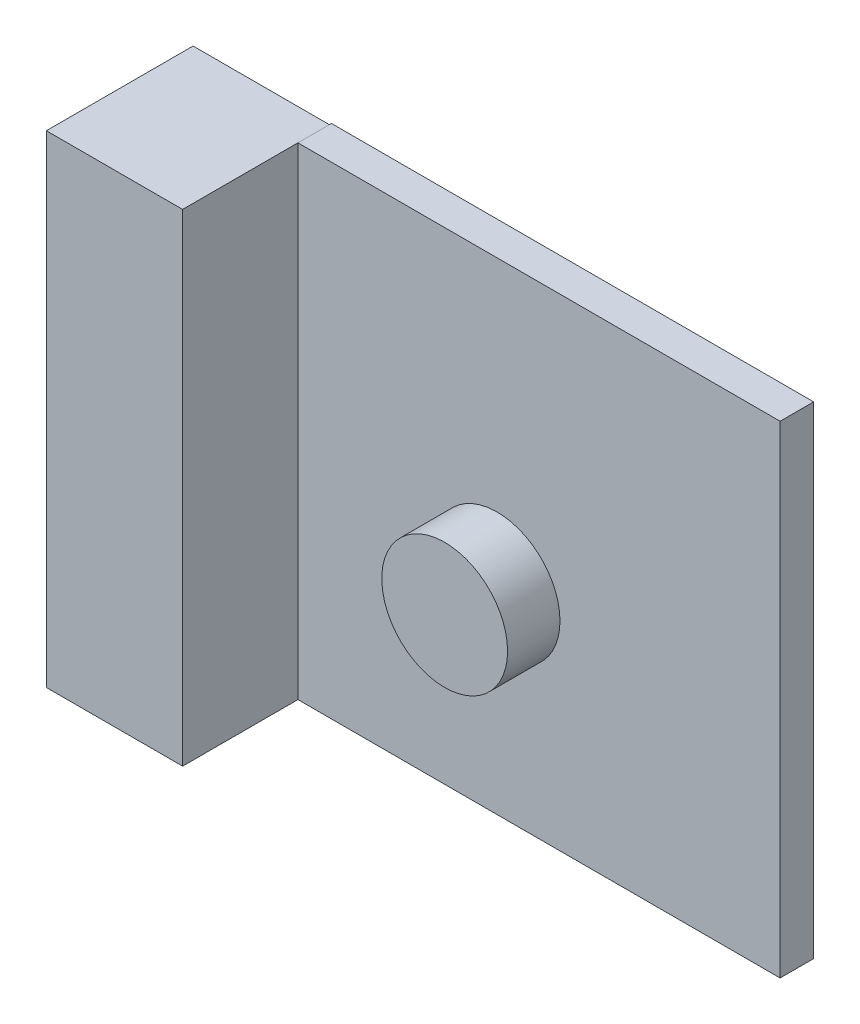
SolidWorks part; units mm, degrees
ref_plane "Front Plane" through (0, 0, 0) normal (0, 0, 1) x (1, 0, 0)
ref_plane "Top Plane" through (0, 0, 0) normal (0, 1, 0) x (1, 0, 0)
ref_plane "Right Plane" through (0, 0, 0) normal (1, 0, 0) x (0, 0, -1)
other "Configuration Table"
sketch "Sketch1" plane through (0, 0, 0) normal (0, 0, 1) x (1, 0, 0)
  circle A0 centre (58, 130) radius 3
extrude "magnet" add sketch "Sketch1" along normal blind 2.5 from offset 35.5 separate body offset against normal yes
sketch "Sketch2" plane through (0, 0, 0) normal (1, 0, 0) x (0, 0, -1)
  line L1 (39.1, 118.5) -> (37.5, 118.5)
  line L2 (39.1, 118.5) -> (39.1, 141.5)
  line L3 (39.1, 141.5) -> (37.5, 141.5)
  line L4 (37.5, 118.5) -> (37.5, 141.5)
  line L5 (39.1, 118.5) -> (37.5, 141.5) construction
  line L6 (39.1, 141.5) -> (37.5, 118.5) construction
  point P0 (38.3, 130)
extrude "as5600_board" add sketch "Sketch2" along normal blind 23 from offset 46.5 separate body
sketch "Sketch3" plane through (0, 0, 0) normal (1, 0, 0) x (0, 0, -1)
  line L0 (35.5, 127) -> (35.5, 133) construction
  line L1 (39, 118.5) -> (32, 118.5)
  line L2 (39, 118.5) -> (39, 141.5)
  line L3 (39, 141.5) -> (32, 141.5)
  line L4 (32, 118.5) -> (32, 141.5)
  line L5 (39, 118.5) -> (32, 141.5) construction
  line L6 (39, 141.5) -> (32, 118.5) construction
  point P0 (35.5, 130)
extrude "sensor_bracket" add sketch "Sketch3" along normal blind 6.5 from offset 40 separate body
